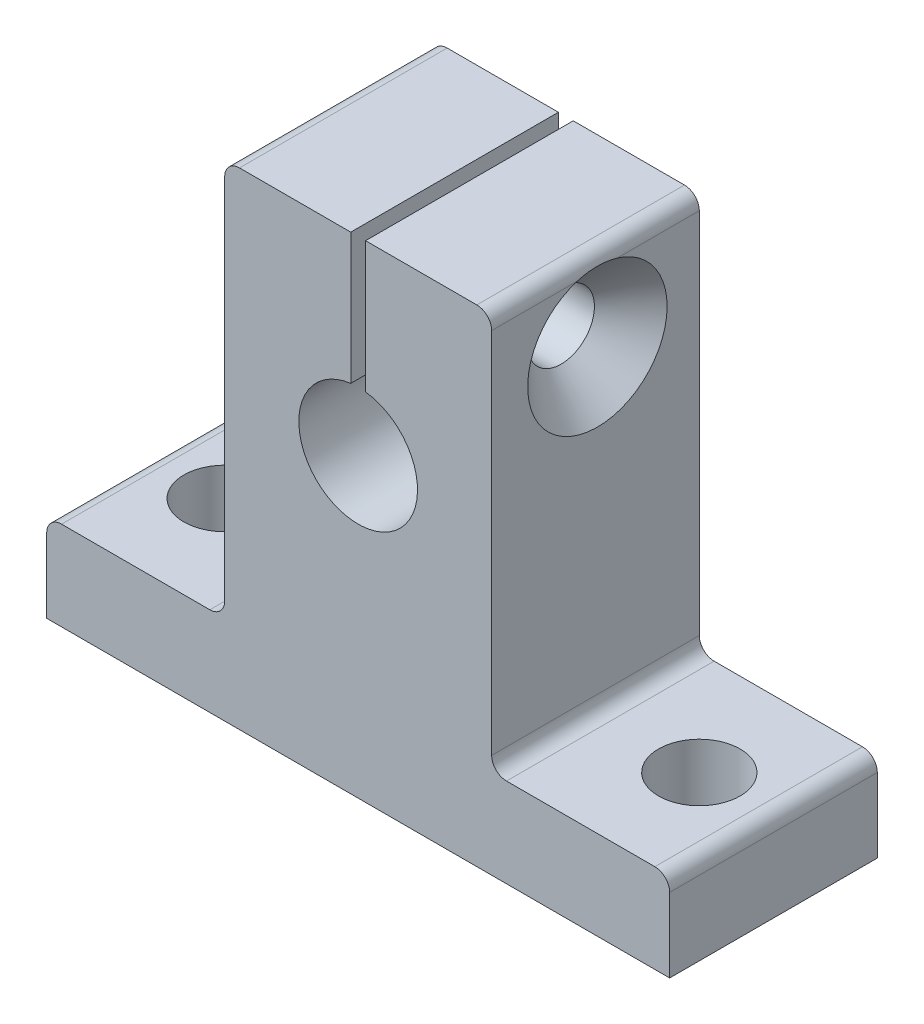
SolidWorks part; units mm, degrees
ref_plane "Front Plane" through (0, 0, 0) normal (0, 0, 1) x (1, 0, 0)
ref_plane "Top Plane" through (0, 0, 0) normal (0, 1, 0) x (1, 0, 0)
ref_plane "Right Plane" through (0, 0, 0) normal (1, 0, 0) x (0, 0, -1)
sketch "Sketch1" plane through (0, 0, 0) normal (0, 0, 1) x (1, 0, 0)
  line L0 (-21, 0) -> (21, 0)
  line L1 (-21, 0) -> (-21, 6)
  line L2 (-21, 6) -> (-9, 6)
  line L3 (-9, 6) -> (-9, 32.8)
  line L4 (-9, 32.8) -> (-0.5, 32.8)
  line L5 (-0.5, 32.8) -> (-0.5, 23.9686)
  line L7 (0.5, 23.9686) -> (0.5, 32.8)
  line L8 (0.5, 32.8) -> (9, 32.8)
  line L9 (9, 32.8) -> (9, 6)
  line L10 (9, 6) -> (21, 6)
  line L11 (21, 6) -> (21, 0)
  arc A0 (-0.5, 23.9686) -> (0.5, 23.9686) centre (0, 20) ccw
  dimension "D4" = 8
  dimension "D1" = 42
  dimension "D2" = 6
  dimension "D3" = 32.8
  dimension "D5" = 20
  dimension "D6" = 18
  dimension "D7" = 1
  dimension "D8" = 9
extrude "Boss-Extrude1" add sketch "Sketch1" along normal blind 14
hole_wizard "Ø5.5 (5.5) Diameter Hole1" positions "3DSketch1" profile "Sketch2" hole size "Ø5.5" standard "ANSI Metric" end condition through all
sketch3d "3DSketch1"
  line L0 (-9, 6, 0) -> (-21, 6, 0) construction
  line L4 (-21, 6, 14) -> (-21, 6, 0) construction
  point P0 (-16, 6, 7)
  point P2 (16, 6, 7)
  dimension "D1" = 7
  dimension "D2" = 32
  dimension "D3" = 5
sketch "Sketch2" plane through (-16, 6, 7) normal (1, 0, 0) x (0, 0, 1)
  line L0 (0, 0) -> (0, 6)
  line L1 (0, 6) -> (2.75, 6)
  line L2 (2.75, 6) -> (2.75, 0)
  line L5 (2.75, 0) -> (0, 0)
  line L11 (0, -6.35) -> (0, 107.95) construction
  dimension "Thru Hole Dia." = 5.5
  dimension "Thru Hole Depth" = 6
hole_wizard "CSK for M4 Flat Head Machine Screw1" positions "3DSketch2" profile "Sketch3" countersink size "M4" standard "ANSI Metric" end condition through all
sketch3d "3DSketch2"
  line L0 (9, 32.8, 14) -> (9, 32.8, 0) construction
  point P0 (9, 27.3, 6.8714)
  dimension "D1" = 5.5
sketch "Sketch3" plane through (9, 27.3, 6.8714) normal (0, 1, 0) x (0, 0, -1)
  line L0 (0, 0) -> (0, 30)
  line L1 (0, 30) -> (2.25, 30)
  line L2 (2.25, 30) -> (2.25, 2.45)
  line L3 (2.25, 2.45) -> (4.7, 0)
  line L5 (4.7, 0) -> (0, 0)
  line L6 (-2.25, 2.45) -> (-4.7, 0) construction
  line L11 (0, -6.35) -> (0, 107.95) construction
  dimension "Thru Hole Dia." = 4.5
  dimension "Thru Hole Depth" = 30
  dimension "Near C'Sink Dia." = 9.4
  dimension "Near C'Sink Angle" = 90
fillet "Fillet1" radius 1 6 edges at (9, 6, 7) (-9, 6, 7) (21, 6, 7) (-21, 6, 7) (9, 32.8, 7) (-9, 32.8, 7)
